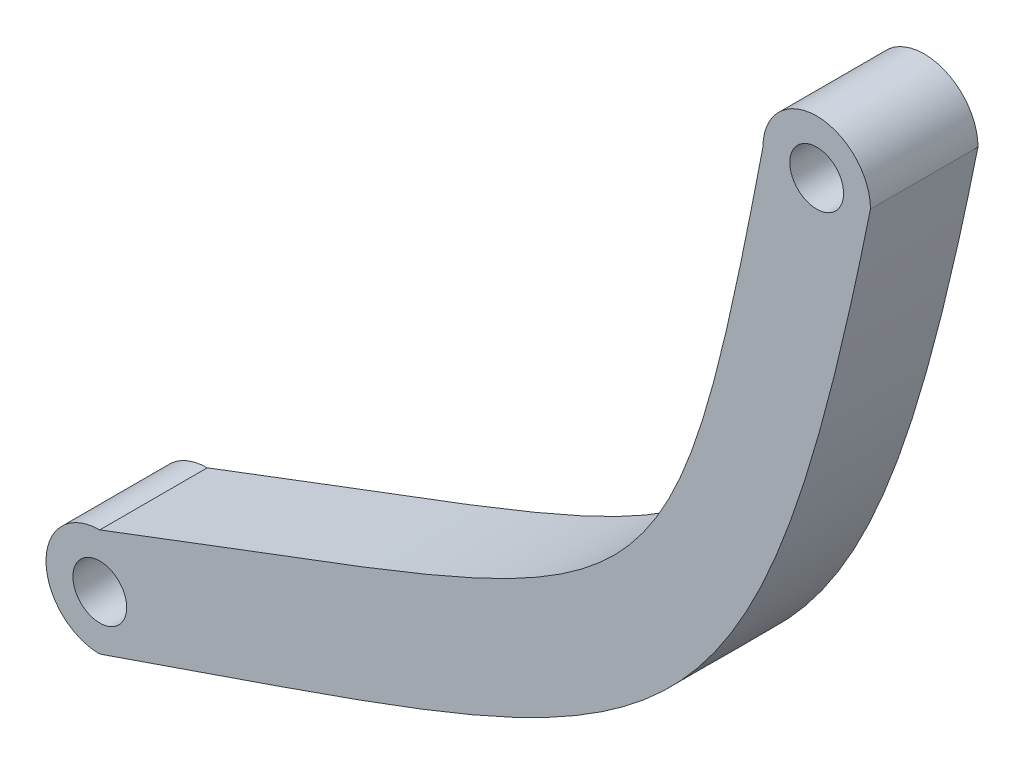
SolidWorks part; units mm, degrees
ref_plane "Plan de face" through (0, 0, 0) normal (0, 0, 1) x (1, 0, 0)
ref_plane "Plan de dessus" through (0, 0, 0) normal (0, 1, 0) x (1, 0, 0)
ref_plane "Plan de droite" through (0, 0, 0) normal (1, 0, 0) x (0, 0, -1)
sketch "Esquisse1" plane through (0, 0, 0) normal (0, 0, 1) x (1, 0, 0)
  line L0 (0, 3) -> (0, -3) construction
  line L1 (43, 40) -> (37, 40) construction
  circle A0 centre (0, 0) radius 1.5
  circle A1 centre (40, 40) radius 1.5
  arc A2 (0, 3) -> (0, -3) centre (0, 0) ccw
  arc A3 (37, 40) -> (43, 40) centre (40, 40) cw
  spline S0 degree 3 poles (0, 3) (31.1157, 14.955) (31.6647, 12.3591) (37, 40) knots 0 0 0 0 1 1 1 1
  spline S1 degree 3 poles (0, -3) (31.4782, 7.9652) (36.3595, 7.3348) (43, 40) knots 0 0 0 0 1 1 1 1
  point P3 (0, 0)
  point P7 (0, -3)
  point P8 (0, -3)
  dimension "D1" = 3
  dimension "D4" = 100
  dimension "D7" = 100
  dimension "D2" = 6
  dimension "D3" = 6
extrude "Boss.-Extru.1" add sketch "Esquisse1" along normal blind 3 and the other way blind 3 contours S1 A3 S0 A2 | A0 | A1
